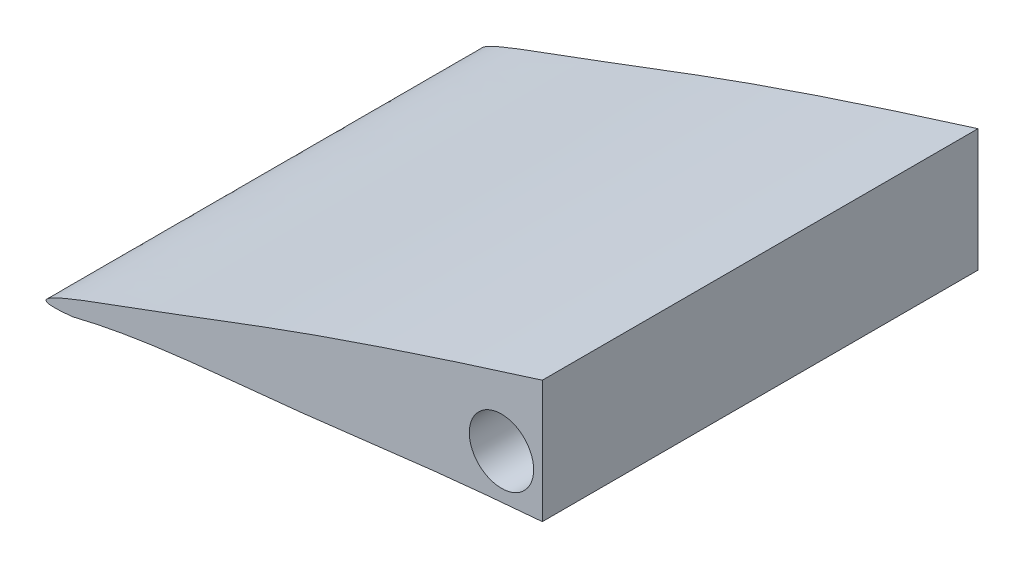
SolidWorks part; units mm, degrees
ref_plane "Front Plane" through (0, 0, 0) normal (0, 0, 1) x (1, 0, 0)
ref_plane "Top Plane" through (0, 0, 0) normal (0, 1, 0) x (1, 0, 0)
ref_plane "Right Plane" through (0, 0, 0) normal (1, 0, 0) x (0, 0, -1)
sketch "Sketch1" plane through (0, 0, 0) normal (0, 0, 1) x (1, 0, 0)
  line L0 (42.9183, -0.4477) -> (42.9183, 8.2631)
  circle A0 centre (-19.1025, -6.0109) radius 2
  circle A1 centre (12.6475, 4.4031) radius 2.127
  arc A2 (37.8951, -5.5274) -> (42.9183, -0.4477) centre (37.8383, -0.4477) ccw
  arc A3 (42.9183, 8.2631) -> (36.6811, 13.2095) centre (37.8383, 8.2631) ccw
  circle A4 centre (33.8935, 3.4217) radius 2.032
  spline S0 degree 3 poles (36.6811, 13.2095) (19.8298, 9.2672) (-2.0736, 3.8441) (-31.0965, -5.5459) (-39.3168, -8.8066) (-49.5156, -12.4957) (-45.7725, -12.1069) knots 0.118069 0.118069 0.118069 0.118069 0.630725 0.824214 0.940085 1 1 1 1
  spline S1 degree 3 poles (-45.7725, -12.1069) (-41.3374, -10.9993) (-33.8316, -10.53) (-20.4835, -8.7075) (-8.8734, -8.0192) (11.5246, -6.0282) (26.0673, -5.6598) (37.8951, -5.5274) knots 0 0 0 0 0.144322 0.237948 0.427123 0.512832 0.887818 0.887818 0.887818 0.887818
  dimension "D2" = 4
  dimension "D1" = 83.6676
extrude "Boss-Extrude1" add sketch "Sketch1" along normal blind 27.0764
sketch "Sketch2" plane through (0, 0, 27.0764) normal (0, 0, 1) x (1, 0, 0)
  line L1 (-16.5625, 14.1188) -> (88.17, 14.1188)
  line L2 (-16.5625, 14.1188) -> (-16.5625, -18.8296)
  line L3 (-16.5625, -18.8296) -> (88.17, -18.8296)
  line L4 (88.17, 14.1188) -> (88.17, -18.8296)
  dimension "D1" = 29.21
extrude "Cut-Extrude1" cut sketch "Sketch2" against normal blind 27.0764
